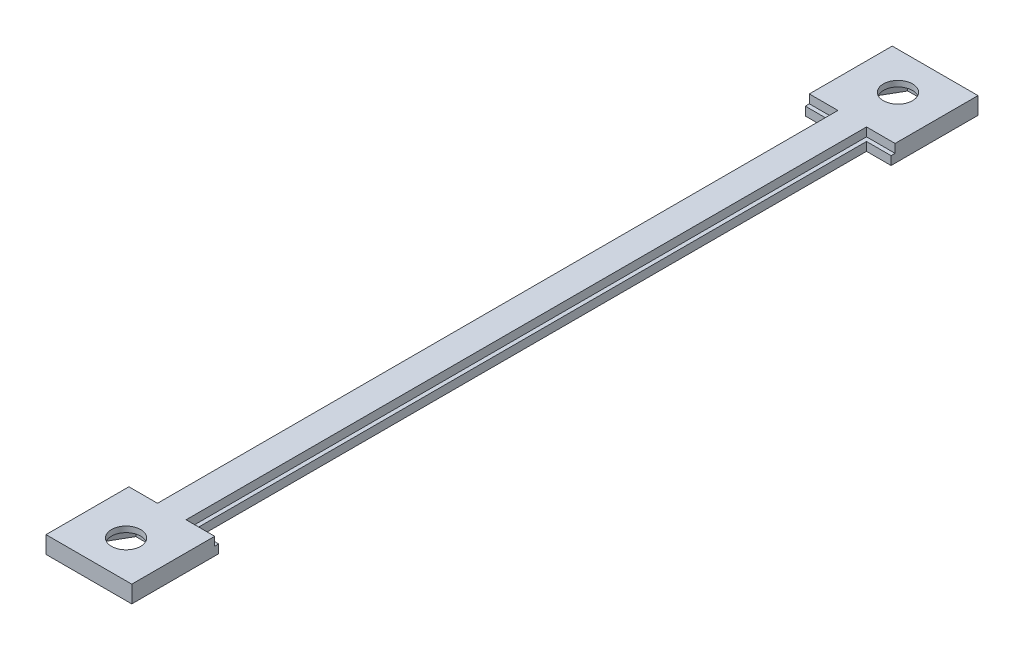
SolidWorks part; units mm, degrees
ref_plane "Front Plane" through (0, 0, 0) normal (0, 0, 1) x (1, 0, 0)
ref_plane "Top Plane" through (0, 0, 0) normal (0, 1, 0) x (1, 0, 0)
ref_plane "Right Plane" through (0, 0, 0) normal (1, 0, 0) x (0, 0, -1)
sketch "Sketch1" plane through (0, 0, 0) normal (0, 1, 0) x (1, 0, 0)
  line L0 (16.0599, 8.247) -> (16.0599, 23.747)
  line L1 (31.0599, 8.247) -> (31.0599, 23.747)
  line L2 (16.0599, 8.247) -> (31.0599, 8.247)
  line L3 (31.0599, 23.747) -> (26.0599, 23.747)
  line L4 (16.0599, 142.747) -> (16.0599, 158.247)
  line L5 (26.0599, 23.747) -> (26.0599, 142.747)
  line L6 (21.0599, 23.747) -> (21.0599, 142.747)
  line L7 (16.0599, 142.747) -> (21.0599, 142.747)
  line L8 (31.0599, 142.747) -> (31.0599, 158.247)
  line L9 (31.0599, 158.247) -> (16.0599, 158.247)
  line L10 (26.0599, 142.747) -> (31.0599, 142.747)
  line L11 (21.0599, 23.747) -> (16.0599, 23.747)
  dimension "D1" = 15
extrude "Boss-Extrude1" add sketch "Sketch1" along normal blind 3
sketch "Sketch2" plane through (0, 0, 0) normal (0, -1, 0) x (-1, 0, 0)
  line L0 (-21.0599, 142.747) -> (-21.0599, 23.747)
  line L1 (-21.0599, 23.747) -> (-16.0599, 23.747)
  line L2 (-31.0599, 23.747) -> (-26.0599, 23.747)
  line L3 (-26.0599, 23.747) -> (-26.0599, 142.747)
  line L4 (-26.0599, 142.747) -> (-31.0599, 142.747)
  line L5 (-21.0599, 142.747) -> (-16.0599, 142.747)
  line L6 (-20.3599, 142.047) -> (-16.0599, 142.047)
  line L7 (-20.3599, 142.047) -> (-20.3599, 24.447)
  line L8 (-20.3599, 24.447) -> (-16.0599, 24.447)
  line L9 (-31.0599, 24.447) -> (-26.7599, 24.447)
  line L10 (-26.7599, 24.447) -> (-26.7599, 142.047)
  line L11 (-26.7599, 142.047) -> (-31.0599, 142.047)
  line L12 (-16.0599, 142.747) -> (-16.0599, 142.047)
  line L13 (-16.0599, 23.747) -> (-16.0599, 24.447)
  line L14 (-31.0599, 23.747) -> (-31.0599, 24.447)
  line L15 (-31.0599, 142.747) -> (-31.0599, 142.047)
  dimension "D1" = 0.7
extrude "Boss-Extrude2" add sketch "Sketch2" against normal blind 2
sketch "Sketch3" plane through (0, 0, 0) normal (0, -1, 0) x (-1, 0, 0)
  line L2 (-16.0599, 158.247) -> (-31.0599, 158.247)
  line L3 (-16.0599, 157.247) -> (-31.0599, 157.247)
  line L4 (-16.0599, 157.247) -> (-16.0599, 158.247)
  line L5 (-31.0599, 158.247) -> (-31.0599, 157.247)
  line L6 (-31.0599, 9.247) -> (-31.0599, 8.247)
  line L7 (-16.0599, 9.247) -> (-31.0599, 9.247)
  line L8 (-16.0599, 8.247) -> (-16.0599, 9.247)
  line L9 (-16.0599, 8.247) -> (-31.0599, 8.247)
  dimension "D1" = 1
extrude "Cut-Extrude1" cut sketch "Sketch3" against normal blind 5
sketch "Sketch4" plane through (0, 0, 0) normal (0, -1, 0) x (-1, 0, 0)
  line L2 (-19.5099, 147.3087) -> (-19.5099, 151.9853)
  line L3 (-23.5599, 12.1705) -> (-19.5099, 14.5087)
  line L4 (-19.5099, 14.5087) -> (-19.5099, 19.1853)
  line L5 (-19.5099, 19.1853) -> (-23.5599, 21.5235)
  line L6 (-23.5599, 21.5235) -> (-27.6099, 19.1853)
  line L7 (-27.6099, 19.1853) -> (-27.6099, 14.5087)
  line L8 (-27.6099, 14.5087) -> (-23.5599, 12.1705)
  line L9 (-23.5599, 154.3235) -> (-27.6099, 151.9853)
  line L10 (-27.6099, 147.3087) -> (-23.5599, 144.9705)
  line L11 (-19.5099, 151.9853) -> (-23.5599, 154.3235)
  line L12 (-23.5599, 144.9705) -> (-19.5099, 147.3087)
  line L14 (-27.6099, 151.9853) -> (-27.6099, 147.3087)
  circle A0 centre (-23.5599, 16.847) radius 4.05 construction
  circle A1 centre (-23.5599, 149.647) radius 4.05 construction
extrude "Cut-Extrude2" cut sketch "Sketch4" against normal blind 1.5
sketch "Sketch5" plane through (0, 1.5, 0) normal (0, -1, 0) x (-1, 0, 0)
  circle A0 centre (-23.5599, 16.847) radius 2.6
  circle A1 centre (-23.5599, 149.647) radius 2.6
extrude "Cut-Extrude3" cut sketch "Sketch5" against normal blind 5
sketch "Sketch6" plane through (0, 2, 0) normal (0, 1, 0) x (1, 0, 0)
  line L0 (16.0599, 142.047) -> (16.0599, 142.747)
  line L1 (16.0599, 142.747) -> (21.0599, 142.747)
  line L2 (21.0599, 142.747) -> (21.0599, 23.747)
  line L3 (21.0599, 23.747) -> (16.0599, 23.747)
  line L4 (16.0599, 23.747) -> (16.0599, 24.447)
  line L5 (16.0599, 24.447) -> (20.3599, 24.447)
  line L6 (20.3599, 142.047) -> (16.0599, 142.047)
  line L7 (20.3599, 142.047) -> (20.3599, 24.447)
  line L8 (31.0599, 23.747) -> (31.0599, 24.447)
  line L9 (31.0599, 24.447) -> (26.7599, 24.447)
  line L10 (26.7599, 24.447) -> (26.7599, 142.047)
  line L11 (26.7599, 142.047) -> (31.0599, 142.047)
  line L12 (31.0599, 142.047) -> (31.0599, 142.747)
  line L13 (31.0599, 142.747) -> (26.0599, 142.747)
  line L14 (26.0599, 142.747) -> (26.0599, 23.747)
  line L15 (26.0599, 23.747) -> (31.0599, 23.747)
extrude "Cut-Extrude4" cut sketch "Sketch6" against normal blind 0.5
sketch "Sketch7" plane through (0, 0, 0) normal (0, -1, 0) x (-1, 0, 0)
  line L0 (-20.3599, 79.447) -> (-26.7599, 79.447)
  line L1 (-20.3599, 29.447) -> (-26.7599, 29.447)
  line L2 (-20.3599, 29.447) -> (-20.3599, 79.447)
  line L3 (-26.7599, 79.447) -> (-26.7599, 29.447)
  dimension "D1" = 50
extrude "Boss-Extrude3" add sketch "Sketch7" along normal blind 25.5
sketch "Sketch8" plane through (0, 0, -79.447) normal (0, 0, -1) x (-1, 0, 0)
  line L0 (-20.3599, -25.5) -> (-26.7599, -25.5)
  arc A0 (-26.7599, -25.5) -> (-20.3599, -25.5) centre (-23.5599, -25.5) ccw
  line M3 (-26.7599, -25.5) -> (-20.3599, -25.5)
extrude "Boss-Extrude5" add sketch "Sketch8" against normal blind 50 contours A0 M3 region at (23.5599, -26.8581, -79.447)
sketch "Sketch9" plane through (0, 1.5, 0) normal (0, -1, 0) x (-1, 0, 0)
  line L1 (-23.5599, 154.3235) -> (-27.6099, 151.9853)
  line L2 (-27.6099, 151.9853) -> (-27.6099, 147.3087)
  line L3 (-27.6099, 147.3087) -> (-23.5599, 144.9705)
  line L4 (-23.5599, 144.9705) -> (-19.5099, 147.3087)
  line L5 (-19.5099, 147.3087) -> (-19.5099, 151.9853)
  line L6 (-19.5099, 151.9853) -> (-23.5599, 154.3235)
  line L7 (-23.5599, 21.5235) -> (-27.6099, 19.1853)
  line L8 (-27.6099, 19.1853) -> (-27.6099, 14.5087)
  line L9 (-27.6099, 14.5087) -> (-23.5599, 12.1705)
  line L10 (-23.5599, 12.1705) -> (-19.5099, 14.5087)
  line L11 (-19.5099, 14.5087) -> (-19.5099, 19.1853)
  line L12 (-19.5099, 19.1853) -> (-23.5599, 21.5235)
  circle A0 centre (-23.5599, 149.647) radius 4.05 construction
  circle A1 centre (-23.5599, 16.847) radius 4.05 construction
extrude "Cut-Extrude5" cut sketch "Sketch9" against normal blind 0.5
sketch "Sketch10" plane through (0, 2, 0) normal (0, -1, 0) x (-1, 0, 0)
  circle A0 centre (-23.5599, 16.847) radius 2.6
  circle A1 centre (-23.5599, 149.647) radius 2.6
extrude "Boss-Extrude6" add sketch "Sketch10" against normal blind 1
sketch "Sketch11" plane through (0, 2, 0) normal (0, -1, 0) x (-1, 0, 0)
  line L7 (-27.6099, 14.5087) -> (-23.5599, 12.1705)
  line L8 (-23.5599, 12.1705) -> (-19.5099, 14.5087)
  line L9 (-19.5099, 14.5087) -> (-19.5099, 19.1853)
  line L10 (-19.5099, 19.1853) -> (-23.5599, 21.5235)
  line L11 (-23.5599, 21.5235) -> (-27.6099, 19.1853)
  line L12 (-27.6099, 19.1853) -> (-27.6099, 14.5087)
  line L13 (-27.6099, 151.9853) -> (-27.6099, 147.3087)
  line L14 (-27.6099, 147.3087) -> (-23.5599, 144.9705)
  line L15 (-23.5599, 144.9705) -> (-19.5099, 147.3087)
  line L16 (-19.5099, 147.3087) -> (-19.5099, 151.9853)
  line L17 (-19.5099, 151.9853) -> (-23.5599, 154.3235)
  line L18 (-23.5599, 154.3235) -> (-27.6099, 151.9853)
  circle A0 centre (-23.5599, 16.847) radius 4.05 construction
  circle A1 centre (-23.5599, 149.647) radius 4.05 construction
extrude "Boss-Extrude7" add sketch "Sketch11" along normal blind 2
sketch "Sketch12" plane through (0, 0, 0) normal (0, -1, 0) x (-1, 0, 0)
  circle A0 centre (-23.5599, 15.747) radius 2.55
  circle A1 centre (-23.5599, 150.747) radius 2.55
extrude "Cut-Extrude6" cut sketch "Sketch12" against normal blind 5
sketch "Sketch13" plane through (0, 0, 0) normal (0, -1, 0) x (-1, 0, 0)
  line L1 (-28.2365, 15.747) -> (-25.8982, 11.697)
  line L2 (-25.8982, 11.697) -> (-21.2217, 11.697)
  line L3 (-21.2217, 11.697) -> (-18.8834, 15.747)
  line L4 (-18.8834, 15.747) -> (-21.2217, 19.797)
  line L5 (-21.2217, 19.797) -> (-25.8982, 19.797)
  line L6 (-25.8982, 19.797) -> (-28.2365, 15.747)
  line L7 (-28.2365, 150.747) -> (-25.8982, 146.697)
  line L8 (-25.8982, 146.697) -> (-21.2217, 146.697)
  line L9 (-21.2217, 146.697) -> (-18.8834, 150.747)
  line L10 (-18.8834, 150.747) -> (-21.2217, 154.797)
  line L11 (-21.2217, 154.797) -> (-25.8982, 154.797)
  line L12 (-25.8982, 154.797) -> (-28.2365, 150.747)
  circle A0 centre (-23.5599, 15.747) radius 4.05 construction
  circle A1 centre (-23.5599, 150.747) radius 4.05 construction
extrude "Cut-Extrude7" cut sketch "Sketch13" against normal blind 2
sketch "Sketch14" plane through (20.3599, 0, 0) normal (-1, 0, 0) x (0, 0, 1)
  line L0 (-29.447, 0) -> (-79.447, 0)
  line L1 (-79.447, 0) -> (-79.447, -28.7)
  line L2 (-79.447, -28.7) -> (-29.447, -28.7)
  line L3 (-29.447, -28.7) -> (-29.447, 0)
extrude "Cut-Extrude8" cut sketch "Sketch14" against normal blind 10
